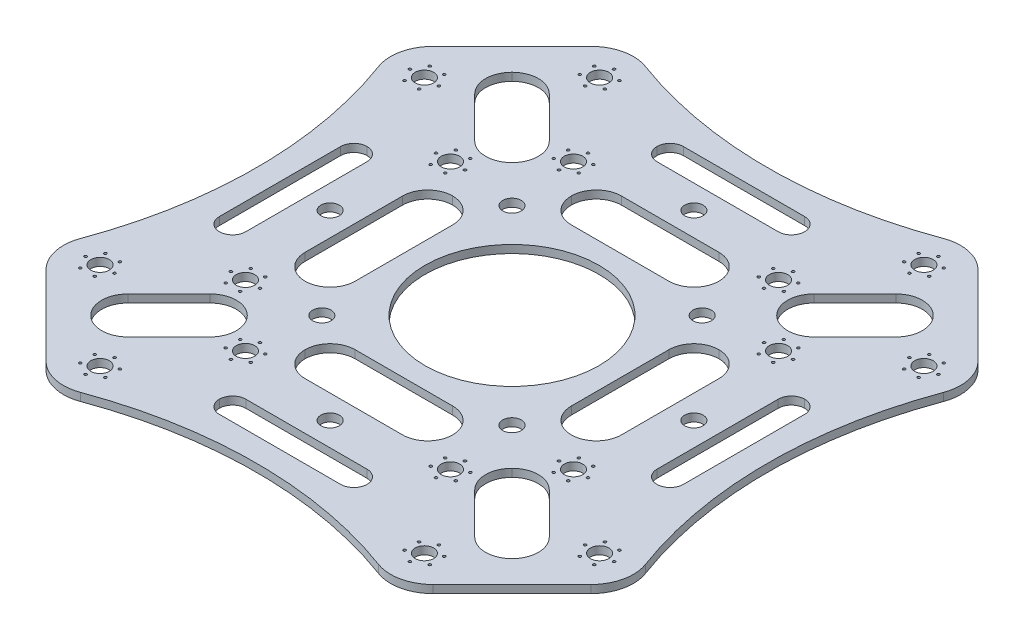
SolidWorks part; units mm, degrees
ref_plane "Front Plane" through (0, 0, 0) normal (0, 0, 1) x (1, 0, 0)
ref_plane "Top Plane" through (0, 0, 0) normal (0, 1, 0) x (1, 0, 0)
ref_plane "Right Plane" through (0, 0, 0) normal (1, 0, 0) x (0, 0, -1)
sketch "Sketch1" plane through (0, 0, 0) normal (0, 1, 0) x (1, 0, 0)
  line L0 (0, 0) -> (0, 130) construction
  line L1 (0, 0) -> (139.2061, 0) construction
  line L2 (0, 0) -> (134.7538, 134.7538) construction
  line L3 (32.9365, 55.4518) -> (55.4518, 32.9365)
  line L4 (-32.9365, 55.4518) -> (-55.4518, 32.9365)
  line L5 (32.9365, -55.4518) -> (55.4518, -32.9365)
  line L6 (-32.9365, -55.4518) -> (-55.4518, -32.9365)
  arc A0 (-32.9365, 55.4518) -> (32.9365, 55.4518) centre (0, 130) ccw
  arc A1 (55.4518, -32.9365) -> (55.4518, 32.9365) centre (130, 0) cw
  arc A2 (-55.4518, -32.9365) -> (-55.4518, 32.9365) centre (-130, 0) ccw
  arc A3 (-32.9365, -55.4518) -> (32.9365, -55.4518) centre (0, -130) cw
  dimension "D3" = 163
  dimension "D2" = 125
  dimension "D4" = 130
extrude "Boss-Extrude1" add sketch "Sketch1" along normal blind 1.5
fillet "Fillet1" radius 8 8 edges at (55.4518, 0.75, 32.9365) (32.9365, 0.75, 55.4518) (-32.9365, 0.75, 55.4518) (-55.4518, 0.75, 32.9365) (-55.4518, 0.75, -32.9365) (-32.9365, 0.75, -55.4518) (32.9365, 0.75, -55.4518) (55.4518, 0.75, -32.9365)
sketch "Sketch2" plane through (0, 1.5, 0) normal (0, 1, 0) x (1, 0, 0)
  line L0 (0, 0) -> (0, 55.0398) construction
  line L1 (-14, 44) -> (14, 44)
  line L2 (-14, 44) -> (-14, 39)
  line L3 (-14, 39) -> (14, 39)
  line L4 (14, 44) -> (14, 39)
  line L5 (-14, 30) -> (14, 30)
  line L6 (-14, 30) -> (-14, 20.5)
  line L7 (-14, 20.5) -> (14, 20.5)
  line L8 (14, 30) -> (14, 20.5)
  line L9 (0, 0) -> (44.1942, 44.1942) construction
  line L10 (51.7063, 36.682) -> (36.682, 51.7063) construction
  line L11 (36.416, 43.4871) -> (21.5668, 28.6378)
  line L12 (43.4871, 36.416) -> (28.6378, 21.5668)
  line L13 (21.5668, 28.6378) -> (28.6378, 21.5668)
  line L14 (36.416, 43.4871) -> (43.4871, 36.416)
  circle A0 centre (0, 0) radius 16.5
  dimension "D1" = 33
  dimension "D2" = 9.5
  dimension "D3" = 28
  dimension "D4" = 28
  dimension "D5" = 9
  dimension "D6" = 5
  dimension "D7" = 6
  dimension "D8" = 21
  dimension "D9" = 10
  dimension "D10" = 20.5
extrude "Cut-Extrude1" cut sketch "Sketch2" against normal through all
fillet "Fillet2" radius 4.75 4 edges at (14, 0.75, -20.5) (14, 0.75, -30) (-14, 0.75, -20.5) (-14, 0.75, -30)
fillet "Fillet3" radius 2.5 4 edges at (14, 0.75, -39) (14, 0.75, -44) (-14, 0.75, -39) (-14, 0.75, -44)
fillet "Fillet4" radius 5 4 edges at (43.4871, 0.75, -36.416) (21.5668, 0.75, -28.6378) (28.6378, 0.75, -21.5668) (36.416, 0.75, -43.4871)
ref_axis "Axis1" through (0, 0, 0) along (0, 1, 0)
pattern_circular "CirPattern1" count 4 over 360 about axis through (0, 0, 0) along (0, 1, 0) of "Cut-Extrude1", "Fillet4", "Fillet3", "Fillet2"
sketch "Sketch3" plane through (0, 1.5, 0) normal (0, 1, 0) x (1, 0, 0)
  line L0 (0, 0) -> (44.1942, 44.1942) construction
  line L1 (51.7063, 36.682) -> (36.682, 51.7063) construction
  line L2 (0, 0) -> (0, 55.2444) construction
  line L3 (9.25, 30) -> (-9.25, 30) construction
  circle A0 centre (30.7591, 47.3762) radius 1.75
  circle A1 centre (19.4454, 31.1127) radius 1.75
  circle A2 centre (18.0312, 18.0312) radius 1.75
  circle A3 centre (0, 34.5) radius 1.75
  circle A4 centre (47.3762, 30.7591) radius 1.75
  circle A5 centre (31.1127, 19.4454) radius 1.75
  dimension "D2" = 3.5
  dimension "D3" = 3.5
  dimension "D4" = 3.5
  dimension "D5" = 3.5
  dimension "D6" = 25.5
  dimension "D1" = 4.5
  dimension "D7" = 7.25
  dimension "D8" = 23.5
  dimension "D9" = 16.5
  dimension "D10" = 26.75
extrude "Cut-Extrude2" cut sketch "Sketch3" against normal through all
pattern_circular "CirPattern2" count 4 over 360 about axis through (0, 0, 0) along (0, 1, 0) of "Cut-Extrude2"
sketch "Sketch4" plane through (0, 1.5, 0) normal (0, 1, 0) x (1, 0, 0)
  circle A2 centre (30.7591, 50.1262) radius 0.25
  circle A3 centre (30.7591, 47.3762) radius 2.75
  circle A4 centre (30.7591, 47.3762) radius 2.75 construction
  circle A5 centre (33.1407, 48.7512) radius 0.25
  circle A6 centre (33.1407, 46.0012) radius 0.25
  circle A7 centre (30.7591, 44.6262) radius 0.25
  circle A8 centre (28.3776, 46.0012) radius 0.25
  circle A9 centre (28.3776, 48.7512) radius 0.25
  point P18 (30.7591, 47.3762)
  dimension "D2" = 0.5
  dimension "D1" = 1
  dimension "D3" = 6
extrude "Cut-Extrude3" cut sketch "Sketch4" against normal through all
ref_plane "Plane1" through (0, 0, 0) normal (0.7071, 0, 0.7071) x (0.7071, 0, -0.7071)
mirror "Mirror1" about plane through (0, 0, 0) normal (0.7071, 0, 0.7071) of "Cut-Extrude3"
pattern_circular "CirPattern3" count 4 over 360 about axis through (0, 0, 0) along (0, 1, 0) of "Cut-Extrude3", "Mirror1"
sketch "Sketch5" plane through (0, 1.5, 0) normal (0, 1, 0) x (1, 0, 0)
  circle A1 centre (19.4454, 33.8627) radius 0.25
  circle A2 centre (19.4454, 31.1127) radius 2.75
  circle A3 centre (19.4454, 31.1127) radius 2.75 construction
  circle A4 centre (21.827, 32.4877) radius 0.25
  circle A5 centre (21.827, 29.7377) radius 0.25
  circle A6 centre (19.4454, 28.3627) radius 0.25
  circle A7 centre (17.0639, 29.7377) radius 0.25
  circle A8 centre (17.0639, 32.4877) radius 0.25
  point P17 (19.4454, 31.1127)
  dimension "D2" = 0.5
  dimension "D1" = 1
  dimension "D3" = 6
extrude "Cut-Extrude4" cut sketch "Sketch5" against normal through all
mirror "Mirror2" about plane through (0, 0, 0) normal (0.7071, 0, 0.7071) of "Cut-Extrude4"
pattern_circular "CirPattern4" count 4 over 360 about axis through (0, 0, 0) along (0, 1, 0) of "Mirror2"
sketch "Sketch6" plane through (0, 0, 0) normal (0, -1, 0) x (1, 0, 0)
  text T0 "ME5763"
extrude "Cut-Extrude5" cut sketch "Sketch6" against normal blind 0.1
